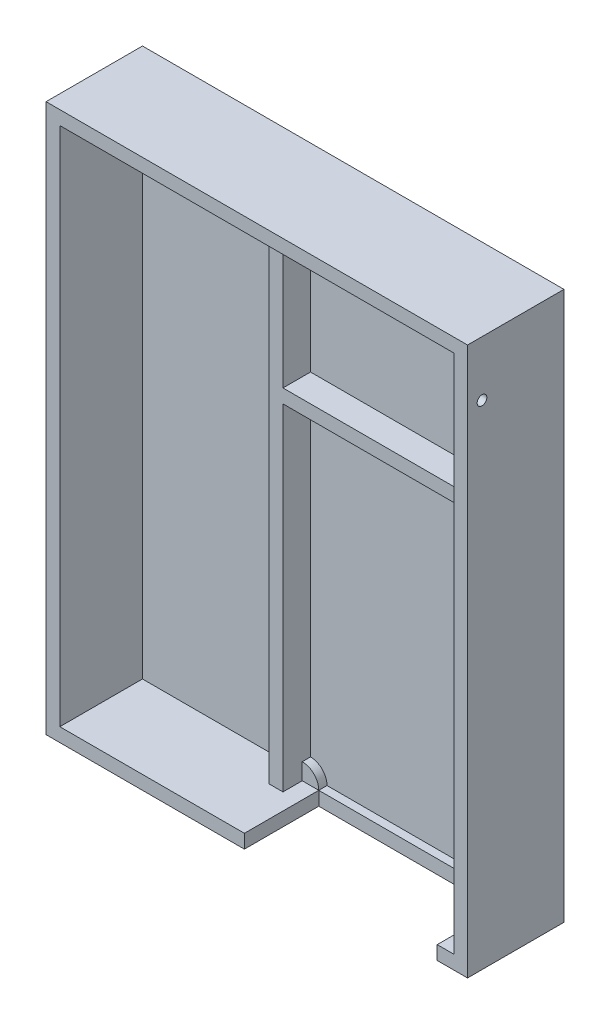
SolidWorks part; units mm, degrees
ref_plane "Front Plane" through (0, 0, 0) normal (1, 0, 0) x (0, 1, 0)
ref_plane "Top Plane" through (0, 0, 0) normal (0, 0, 1) x (0, 1, 0)
ref_plane "Right Plane" through (0, 0, 0) normal (0, 1, 0) x (-1, 0, 0)
sketch "Sketch1" plane through (0, 0, 0) normal (0, 0, 1) x (0, 1, 0)
  line L1 (0, 153) -> (199, 153)
  line L2 (0, 153) -> (0, 0)
  line L3 (0, 0) -> (199, 0)
  line L4 (199, 153) -> (199, 0)
  line L5 (5, 148) -> (172, 148) construction
  line L6 (5, 148) -> (5, 92) construction
  line L7 (5, 92) -> (172, 92) construction
  line L8 (172, 148) -> (172, 92) construction
  line L9 (5, 87) -> (127, 87) construction
  line L10 (5, 87) -> (5, 5) construction
  line L11 (5, 5) -> (127, 5) construction
  line L12 (127, 87) -> (127, 5) construction
  line L13 (132, 87) -> (194, 87) construction
  line L14 (132, 87) -> (132, 5) construction
  line L15 (132, 5) -> (194, 5) construction
  line L16 (194, 87) -> (194, 5) construction
  point P0 (0, 0)
  dimension "D1" = 167
  dimension "D2" = 56
  dimension "D3" = 122
  dimension "D4" = 82
  dimension "D5" = 5
  dimension "D6" = 5
  dimension "D7" = 5
  dimension "D8" = 5
  dimension "D9" = 5
  dimension "D10" = 5
  dimension "D11" = 5
  dimension "D12" = 92
  dimension "D13" = 62
  dimension "D14" = 5
  dimension "D15" = 5
extrude "Boss-Extrude1" add sketch "Sketch1" against normal blind 5
sketch "Sketch2" plane through (0, 0, 0) normal (0, 0, 1) x (1, 0, 0)
  line L0 (-92, 5) -> (-92, 172) construction
  line L1 (-153, 199) -> (0, 199)
  line L2 (-153, 199) -> (-153, 0)
  line L3 (-153, 0) -> (0, 0)
  line L4 (0, 199) -> (0, 0)
  line L5 (-5, 5) -> (-87, 5)
  line L6 (-5, 5) -> (-5, 127)
  line L7 (-5, 127) -> (-87, 127)
  line L8 (-87, 5) -> (-87, 127)
  line L9 (-87, 132) -> (-5, 132)
  line L10 (-87, 132) -> (-87, 194)
  line L11 (-87, 194) -> (-5, 194)
  line L12 (-5, 132) -> (-5, 194)
  line L13 (-148, 5) -> (-92, 5)
  line L14 (-148, 5) -> (-148, 194)
  line L15 (-148, 194) -> (-92, 194)
  line L16 (-92, 5) -> (-92, 194)
extrude "Boss-Extrude2" add sketch "Sketch2" along normal blind 10
sketch "Sketch3" plane through (0, 0, 10) normal (0, 0, 1) x (1, 0, 0)
  line L1 (-148, 194) -> (-5, 194)
  line L2 (-148, 194) -> (-148, 5)
  line L3 (-148, 5) -> (-5, 5)
  line L4 (-5, 194) -> (-5, 5)
  line L5 (0, 0) -> (-153, 0)
  line L6 (0, 0) -> (0, 199)
  line L7 (0, 199) -> (-153, 199)
  line L8 (-153, 0) -> (-153, 199)
extrude "Boss-Extrude3" add sketch "Sketch3" along normal blind 20
sketch "Sketch4" plane through (0, 0, 0) normal (0, 0, 1) x (1, 0, 0)
  line L0 (-87, 66) -> (-5, 66) construction
  line L1 (-87, 127) -> (-81, 127)
  line L2 (-87, 127) -> (-87, 121)
  line L3 (-87, 121) -> (-81, 121)
  line L4 (-81, 127) -> (-81, 121)
  line L5 (-87, 127) -> (-87, 5) construction
  line L6 (-5, 5) -> (-5, 127) construction
  line L7 (-46, 127) -> (-46, 5) construction
  line L8 (-5, 127) -> (-87, 127) construction
  line L9 (-87, 5) -> (-5, 5) construction
  line L10 (-11, 127) -> (-11, 121)
  line L11 (-5, 121) -> (-11, 121)
  line L12 (-5, 127) -> (-5, 121)
  line L13 (-5, 127) -> (-11, 127)
  line L14 (-5, 5) -> (-11, 5)
  line L15 (-5, 5) -> (-5, 11)
  line L16 (-5, 11) -> (-11, 11)
  line L17 (-11, 5) -> (-11, 11)
  line L18 (-81, 5) -> (-81, 11)
  line L19 (-87, 11) -> (-81, 11)
  line L20 (-87, 5) -> (-87, 11)
  line L21 (-87, 5) -> (-81, 5)
  dimension "D1" = 6
extrude "Boss-Extrude4" add sketch "Sketch4" along normal blind 3
fillet "Fillet1" radius 6 4 edges at (-81, 11, 1.5) (-11, 11, 1.5) (-81, 121, 1.5) (-11, 121, 1.5)
sketch "Sketch5" plane through (0, 0, 30) normal (0, 0, 1) x (1, 0, 0)
  line L0 (-87, 5) -> (-81, 5) construction
  line L1 (-148, 5) -> (-5, 5) construction
  line L2 (-11, 5) -> (-5, 5) construction
  line L3 (-81, 5) -> (-11, 5)
  line L4 (-81, 5) -> (-11, 5) construction
  line L5 (-81, 5) -> (-81, 0)
  line L6 (-153, 0) -> (0, 0) construction
  line L7 (-81, 0) -> (-11, 0)
  line L8 (-11, 0) -> (-11, 5)
  dimension "D1" = 6
extrude "Cut-Extrude1" cut sketch "Sketch5" against normal up to surface (27 mm away) contours L3 L8 L7 L5 up to face at (-84.5858, 7.4142, 3)
sketch "Sketch6" plane through (-5, 0, 0) normal (-1, 0, 0) x (0, -1, 0)
  line L1 (-5, 30) -> (-194, 30) construction
  line L2 (-179, 26.5) -> (-179, 30) construction
  line L3 (-199, -5) -> (-199, 30) construction
  circle A0 centre (-179, 24.75) radius 1.75
  dimension "D2" = 3.5
  dimension "D3" = 3.5
  dimension "D1" = 20
extrude "Cut-Extrude2" cut sketch "Sketch6" against normal up to surface (5 mm away) up to face at (0, 99.5, 12.5)
